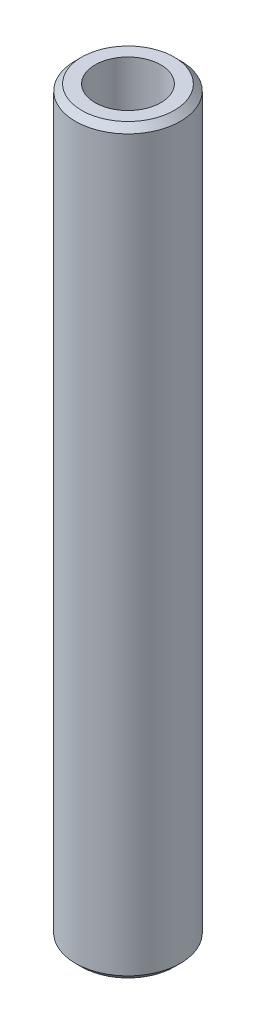
SolidWorks part; units mm, degrees
ref_plane "Front Plane" through (0, 0, 0) normal (0, 0, 1) x (1, 0, 0)
ref_plane "Top Plane" through (0, 0, 0) normal (0, 1, 0) x (1, 0, 0)
ref_plane "Right Plane" through (0, 0, 0) normal (1, 0, 0) x (0, 0, -1)
sketch "Sketch1" plane through (0, 0, 0) normal (0, 1, 0) x (1, 0, 0)
  circle A0 centre (0, 0) radius 42.5
  dimension "SHAFT_OD" = 85
extrude "Boss-Extrude1" add sketch "Sketch1" along normal blind 600
sketch "Sketch2" plane through (0, 0, 0) normal (0, 1, 0) x (1, 0, 0)
  circle A0 centre (0, 0) radius 26.5686
  dimension "BORE_D" = 53.1372
extrude "Cut-Extrude1" cut sketch "Sketch2" along normal through all
chamfer "Chamfer1" distance 5.0831 angle 45 2 edges at (0, 600, 42.5) (0, 0, 42.5)
